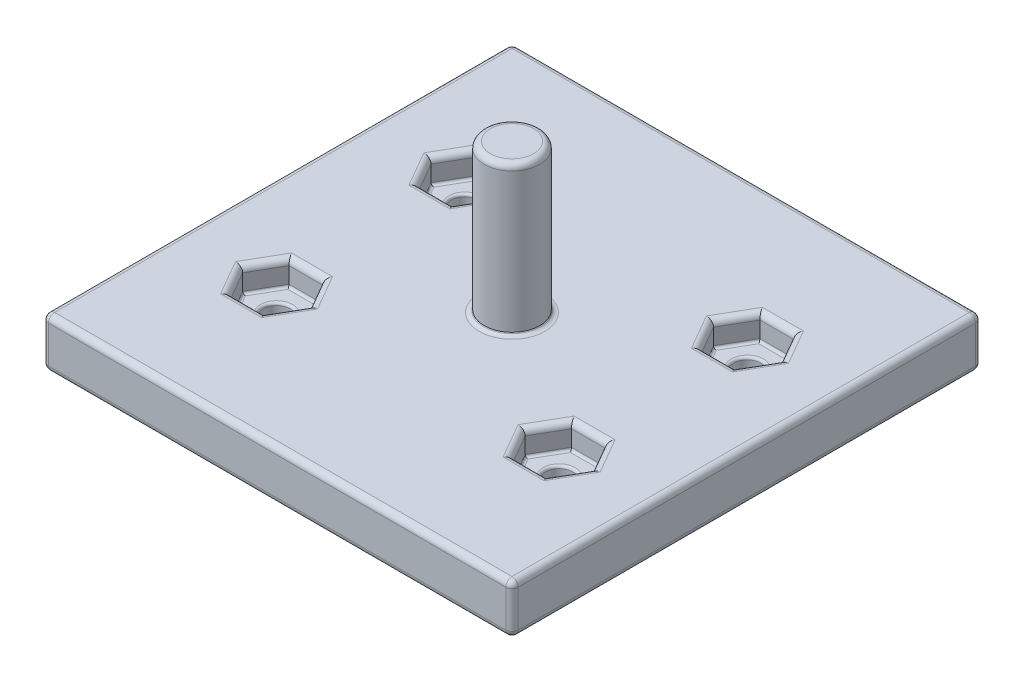
SolidWorks part; units mm, degrees
ref_plane "Front Plane" through (0, 0, 0) normal (0, 0, 1) x (1, 0, 0)
ref_plane "Top Plane" through (0, 0, 0) normal (0, 1, 0) x (1, 0, 0)
ref_plane "Right Plane" through (0, 0, 0) normal (1, 0, 0) x (0, 0, -1)
sketch "Sketch2" plane through (0, 0, 0) normal (0, 1, 0) x (1, 0, 0)
  line L0 (-8.6876, 7.62) -> (-10.0588, 9.995)
  line L1 (-19, -19) -> (19, -19)
  line L2 (-19, -19) -> (-19, 19)
  line L3 (-19, 19) -> (19, 19)
  line L4 (19, -19) -> (19, 19)
  line L5 (-19, -19) -> (19, 19) construction
  line L6 (-19, 19) -> (19, -19) construction
  line L7 (-13.97, -10.16) -> (13.97, -10.16) construction
  line L8 (-13.97, -10.16) -> (-13.97, 10.16) construction
  line L9 (-13.97, 10.16) -> (13.97, 10.16) construction
  line L10 (13.97, -10.16) -> (13.97, 10.16) construction
  line L11 (-13.97, -10.16) -> (13.97, 10.16) construction
  line L12 (-13.97, 10.16) -> (13.97, -10.16) construction
  line L13 (-11.43, -7.62) -> (11.43, -7.62) construction
  line L14 (-11.43, -7.62) -> (-11.43, 7.62) construction
  line L15 (-11.43, 7.62) -> (11.43, 7.62) construction
  line L16 (11.43, -7.62) -> (11.43, 7.62) construction
  line L17 (-11.43, -7.62) -> (11.43, 7.62) construction
  line L18 (-11.43, 7.62) -> (11.43, -7.62) construction
  line L19 (14.1724, 7.62) -> (12.8012, 9.995)
  line L20 (12.8012, 9.995) -> (10.0588, 9.995)
  line L21 (10.0588, 9.995) -> (8.6876, 7.62)
  line L22 (8.6876, 7.62) -> (10.0588, 5.245)
  line L23 (10.0588, 5.245) -> (12.8012, 5.245)
  line L24 (12.8012, 5.245) -> (14.1724, 7.62)
  line L25 (-10.0588, 9.995) -> (-12.8012, 9.995)
  line L26 (-12.8012, 9.995) -> (-14.1724, 7.62)
  line L27 (-14.1724, 7.62) -> (-12.8012, 5.245)
  line L28 (-12.8012, 5.245) -> (-10.0588, 5.245)
  line L29 (-10.0588, 5.245) -> (-8.6876, 7.62)
  line L30 (-8.6876, -7.62) -> (-10.0588, -5.245)
  line L31 (-10.0588, -5.245) -> (-12.8012, -5.245)
  line L32 (-12.8012, -5.245) -> (-14.1724, -7.62)
  line L33 (-14.1724, -7.62) -> (-12.8012, -9.995)
  line L34 (-12.8012, -9.995) -> (-10.0588, -9.995)
  line L35 (-10.0588, -9.995) -> (-8.6876, -7.62)
  line L36 (14.1724, -7.62) -> (12.8012, -5.245)
  line L37 (12.8012, -5.245) -> (10.0588, -5.245)
  line L38 (10.0588, -5.245) -> (8.6876, -7.62)
  line L39 (8.6876, -7.62) -> (10.0588, -9.995)
  line L40 (10.0588, -9.995) -> (12.8012, -9.995)
  line L41 (12.8012, -9.995) -> (14.1724, -7.62)
  circle A0 centre (11.43, 7.62) radius 1.1
  circle A1 centre (11.43, 7.62) radius 2.375 construction
  circle A2 centre (-11.43, 7.62) radius 1.1
  circle A3 centre (-11.43, -7.62) radius 1.1
  circle A4 centre (11.43, -7.62) radius 1.1
  circle A5 centre (0, 0) radius 2.25
  point P0 (0, 0)
  point P6 (0, 0)
  point P11 (0, 0)
  dimension "D7" = 2.2
  dimension "D8" = 4.75
  dimension "D11" = 4.5
  dimension "D1" = 38
  dimension "D2" = 38
  dimension "D3" = 27.94
  dimension "D4" = 20.32
  dimension "D5" = 22.86
  dimension "D6" = 15.24
  dimension "D9" = 2
  dimension "D10" = 2
extrude "Boss-Extrude1" add sketch "Sketch2" along normal blind 2 contours L1 L4 L3 L2 L41 L40 L39 L38 L37 L36 L35 L34 L33 L32 L31 L30 L29 L28 L27 L26 L25 L0 L24 L23 L22 L21 L20 L19 region at (-18.4626, 0, 0)
extrude "Boss-Extrude2" add sketch "Sketch2<3>" against normal blind 2 contours L1 L4 L3 L2 L41 L40 L39 L38 L37 L36 L35 L34 L33 L32 L31 L30 L29 L28 L27 L26 L25 L0 L24 L23 L22 L21 L20 L19 | L28 L29 L0 L25 L26 L27 A2 | L23 L24 L19 L20 L21 L22 A0 | L40 L41 L36 L37 L38 L39 A4 | L34 L35 L30 L31 L32 L33 A3 region at (-9.436, 0, -6.4688) region at (-18.4626, 0, 0) region at (13.424, 0, -6.4688) region at (-9.436, 0, 8.7712) region at (13.424, 0, 8.7712)
sketch "Sketch2<3>" plane through (0, 0, 0) normal (0, 1, 0) x (1, 0, 0) same geometry as "Sketch2"
extrude "Boss-Extrude3" add sketch "Sketch2<4>" against normal blind 2 and the other way blind 14 contours A5 region at (0, 0, 0)
sketch "Sketch2<4>" plane through (0, 0, 0) normal (0, 1, 0) x (1, 0, 0) same geometry as "Sketch2"
chamfer "Chamfer1" distance 0.2 angle 45 1 edges at (0, 2, 2.25)
fillet "Fillet1" radius 0.5 1 edges at (0, 14, 2.25)
fillet "Fillet2" radius 0.5 41 edges at (13.4868, 2, -8.8075) (11.43, 2, -9.995) (9.3732, 2, -8.8075) (9.3732, 2, -6.4325) (11.43, 2, -5.245) (13.4868, 2, -6.4325) (-9.3732, 2, -8.8075) (-11.43, 2, -9.995) (-13.4868, 2, -8.8075) (-13.4868, 2, -6.4325) (-11.43, 2, -5.245) (-9.3732, 2, -6.4325) (-9.3732, 2, 6.4325) (-11.43, 2, 5.245) (-13.4868, 2, 6.4325) (-13.4868, 2, 8.8075) (-11.43, 2, 9.995) (-9.3732, 2, 8.8075) (13.4868, 2, 6.4325) (11.43, 2, 5.245) (9.3732, 2, 6.4325) (9.3732, 2, 8.8075) (11.43, 2, 9.995) (13.4868, 2, 8.8075) (0, 2, 2.45) (11.43, -2, 8.72) (-11.43, -2, 8.72) (-11.43, -2, -6.52) (11.43, -2, -6.52) (-19, 2, 0) (-19, -2, 0) (0, 2, 19) (0, -2, 19) (-19, 0, 19) (19, 2, 0) (19, -2, 0) (19, 0, 19) (0, 2, -19) (-19, 0, -19) (0, -2, -19) (19, 0, -19)
fillet "Fillet3" radius 0.2 28 edges at (11.43, 0, 8.72) (9.3732, 0, 8.8075) (9.3732, 0, 6.4325) (11.43, 0, 5.245) (13.4868, 0, 6.4325) (13.4868, 0, 8.8075) (11.43, 0, 9.995) (11.43, 0, -6.52) (9.3732, 0, -6.4325) (9.3732, 0, -8.8075) (11.43, 0, -9.995) (13.4868, 0, -8.8075) (13.4868, 0, -6.4325) (11.43, 0, -5.245) (-11.43, 0, 8.72) (-13.4868, 0, 8.8075) (-13.4868, 0, 6.4325) (-11.43, 0, 5.245) (-9.3732, 0, 6.4325) (-9.3732, 0, 8.8075) (-11.43, 0, 9.995) (-11.43, 0, -6.52) (-13.4868, 0, -6.4325) (-13.4868, 0, -8.8075) (-11.43, 0, -9.995) (-9.3732, 0, -8.8075) (-9.3732, 0, -6.4325) (-11.43, 0, -5.245)
